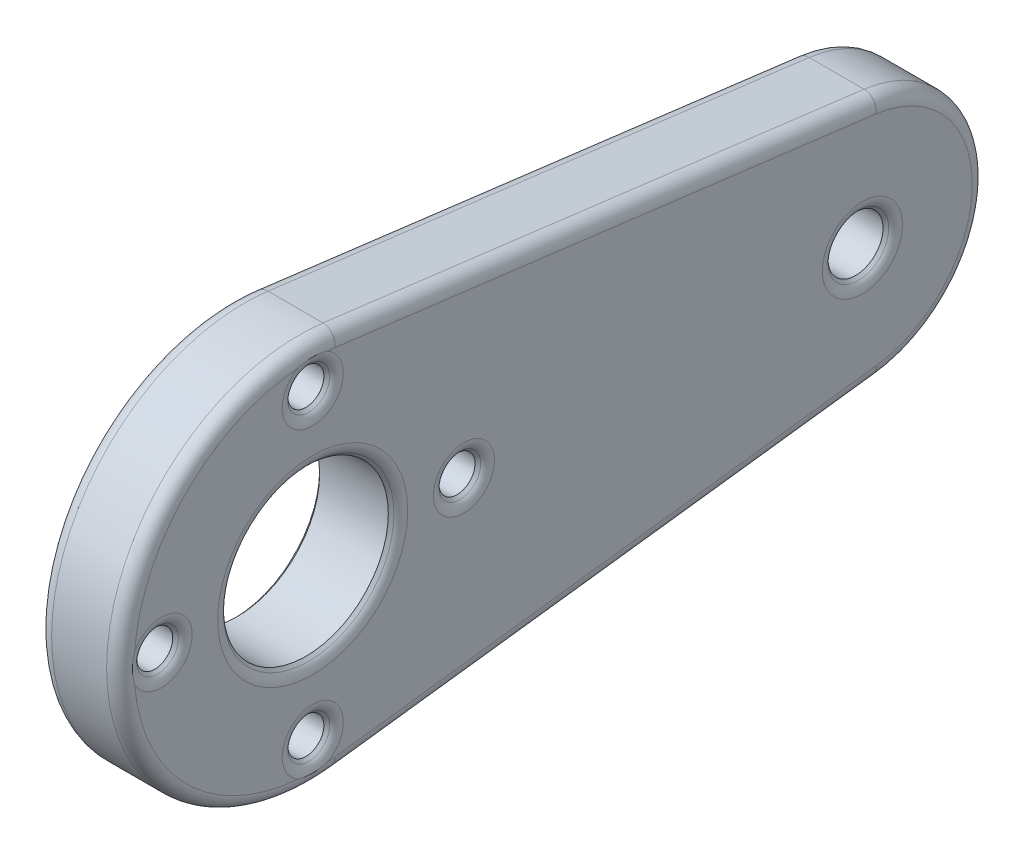
SolidWorks part; units mm, degrees
ref_plane "前视基准面" through (0, 0, 0) normal (0, 0, 1) x (1, 0, 0)
ref_plane "上视基准面" through (0, 0, 0) normal (0, 1, 0) x (1, 0, 0)
ref_plane "右视基准面" through (0, 0, 0) normal (1, 0, 0) x (0, 0, -1)
sketch "草图1" plane through (0, 0, 0) normal (1, 0, 0) x (0, 0, -1)
  line L0 (1.75, 13.8902) -> (41.125, 8.9294)
  line L1 (0, -14.1107) -> (41.125, -8.9294)
  arc A0 (1.75, 13.8902) -> (1.75, -13.8902) centre (0, 0) ccw
  arc A1 (41.125, -8.9294) -> (41.125, 8.9294) centre (40, 0) ccw
  dimension "D1" = 28
  dimension "D2" = 18
  dimension "D3" = 40
extrude "凸台-拉伸1" add sketch "草图1" along normal blind 6 contours L1 A1 L0 A0 region at (0, 0, -15.3781)
sketch "草图2" plane through (0, 0, 0) normal (-1, 0, 0) x (0, 0, 1)
  line L0 (11, 0) -> (0, 0) construction
  line L3 (-41.125, -8.9294) -> (-1.75, -13.8902)
  line L4 (-1.75, 13.8902) -> (-41.125, 8.9294)
  line L5 (-41.125, -8.9294) -> (-1.75, -13.8902)
  line L6 (-1.75, 13.8902) -> (-41.125, 8.9294)
  circle A0 centre (0, 0) radius 6
  circle A2 centre (11, 0) radius 1.3108
  circle A3 centre (0, -11) radius 1.3108
  circle A4 centre (-11, 0) radius 1.3108
  circle A5 centre (0, 11) radius 1.3108
  circle A9 centre (-40, 0) radius 2
  arc A12 (-1.75, -13.8902) -> (-1.75, 13.8902) centre (0, 0) ccw
  arc A13 (-41.125, 8.9294) -> (-41.125, -8.9294) centre (-40, 0) ccw
  arc A14 (-1.75, -13.8902) -> (-1.75, 13.8902) centre (0, 0) ccw
  arc A15 (-41.125, 8.9294) -> (-41.125, -8.9294) centre (-40, 0) ccw
  point P14 (0, 0)
  dimension "D1" = 12
  dimension "D3" = 2.6216
  dimension "D8" = 4
  dimension "D2" = 11
  dimension "D5" = 15.5563
  dimension "D6" = 11
  dimension "D7" = 0
  dimension "D4" = 4
extrude "切除-拉伸1" cut sketch "草图2" against normal through all flip side to cut
chamfer "倒角1" distance 0.5 angle 45 12 edges at (0, 0, 12.3108) (6, 0, 12.3108) (0, -11, 1.3108) (6, -11, 1.3108) (0, 11, 1.3108) (6, 11, 1.3108) (0, 0, 6) (6, 0, 6) (0, 0, -9.6892) (6, 0, -9.6892) (0, 0, -38) (6, 0, -38)
fillet "圆角1" radius 1 20 edges at (6, 0, 14) (6, 11.4098, -21.4375) (6, 0, -49) (6, -11.4098, -21.4375) (6, 0, -42.5) (6, 0, -12.8108) (6, 0, -6.5) (6, 11, -1.8108) (6, -11, -1.8108) (6, 0, 9.1892) (0, 0, -49) (0, 11.4098, -21.4375) (0, 0, 14) (0, -11.4098, -21.4375) (0, 0, -42.5) (0, 0, -12.8108) (0, 0, -6.5) (0, 11, -1.8108) (0, -11, -1.8108) (0, 0, 9.1892)
